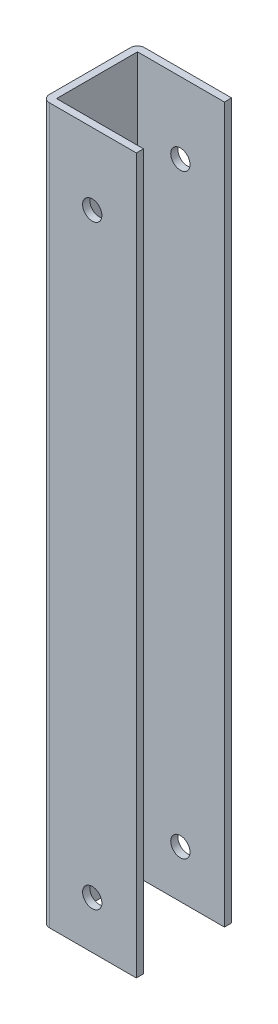
SolidWorks part; units mm, degrees
ref_plane "Спереди" through (0, 0, 0) normal (0, 0, 1) x (1, 0, 0)
ref_plane "Сверху" through (0, 0, 0) normal (0, 1, 0) x (1, 0, 0)
ref_plane "Справа" through (0, 0, 0) normal (1, 0, 0) x (0, 0, -1)
sketch "Эскиз1" plane through (0, 0, 0) normal (0, 1, 0) x (1, 0, 0)
  line L1 (-37, 20) -> (37, 20)
  line L2 (-40, 17) -> (-40, -17)
  line L3 (-37, -20) -> (37, -20)
  line L4 (40, 17) -> (40, -17)
  line L5 (-40, 20) -> (40, -20) construction
  line L6 (-40, -20) -> (40, 20) construction
  arc A0 (-37, 20) -> (-40, 17) centre (-37, 17) ccw
  arc A1 (-40, -17) -> (-37, -20) centre (-37, -17) ccw
  arc A2 (37, -20) -> (40, -17) centre (37, -17) ccw
  arc A3 (37, 20) -> (40, 17) centre (37, 17) cw
  point P0 (0, 0)
  dimension "D1" = 3
extrude "Вытянуть-Тонкостенный1" add sketch "Эскиз1" along normal blind 300 thin thin type one direction reverse wall 3
sketch "Эскиз2" plane through (0, 300, 0) normal (0, 1, 0) x (1, 0, 0)
  line L1 (-0.5, -21.5541) -> (41.1465, -21.5541)
  line L2 (-0.5, -21.5541) -> (-0.5, 20.9728)
  line L3 (-0.5, 20.9728) -> (41.1465, 20.9728)
  line L4 (41.1465, -21.5541) -> (41.1465, 20.9728)
  point P4 (0, 0)
extrude "Вырез-Вытянуть1" cut sketch "Эскиз2" against normal through all
sketch "Эскиз3" plane through (0, 0, -20) normal (0, 0, -1) x (-1, 0, 0)
  circle A0 centre (19, 270) radius 4.05
  circle A1 centre (19, 20) radius 4.05
  dimension "D1" = 2
extrude "Вырез-Вытянуть2" cut sketch "Эскиз3" against normal through all
